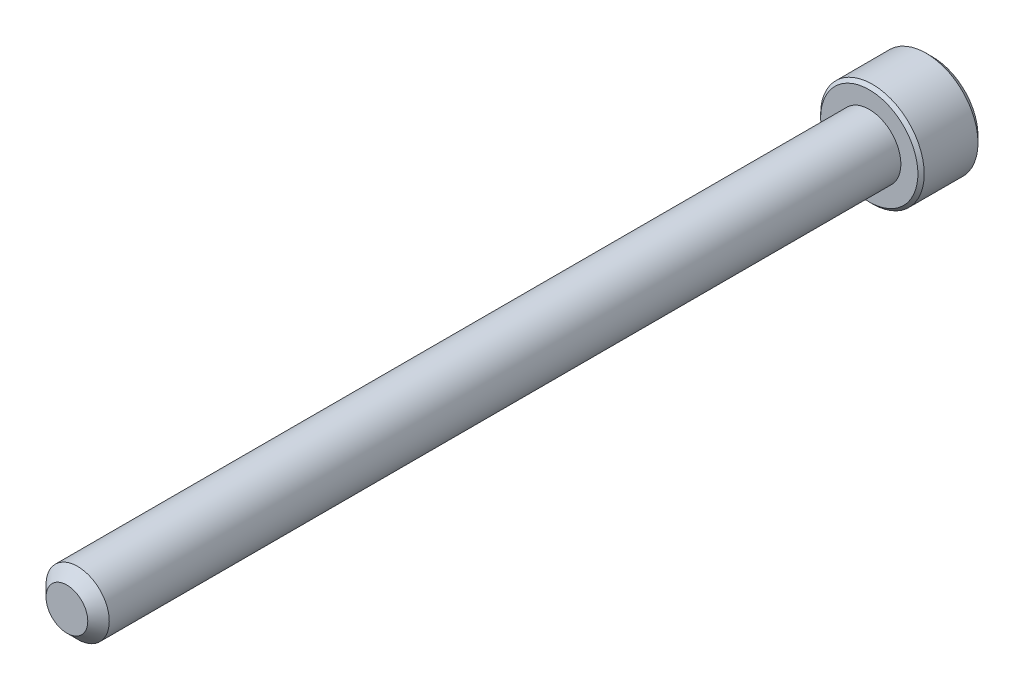
SolidWorks part; units mm, degrees
ref_plane "Front Plane" through (0, 0, 0) normal (0, 0, 1) x (1, 0, 0)
ref_plane "Top Plane" through (0, 0, 0) normal (0, 1, 0) x (1, 0, 0)
ref_plane "Right Plane" through (0, 0, 0) normal (1, 0, 0) x (0, 0, -1)
sketch "Sketch1" plane through (0, 0, 0) normal (0, 0, 1) x (1, 0, 0)
  line L0 (0, 1.7526) -> (0, -1.7526) construction
  circle A0 centre (0, 0) radius 1.7526
  dimension "OD" = 3.5052
extrude "Extrude1" add sketch "Sketch1" against normal blind 44.45
sketch "Sketch2" plane through (0, 0, 0) normal (0, 0, 1) x (1, 0, 0)
  circle A0 centre (0, 0) radius 1.7526 construction
  circle A1 centre (0, 0) radius 1.7526
curve "Helix/Spiral1" pitch 0.7937 height 20.6375 turns 26 parameters "pitch"=0.7937
chamfer "Chamfer3" distance 0.5953 angle 45 1 edges at (1.7526, 0, 0)
sketch "Sketch3" plane through (0, 0, 0) normal (1, 0, 0) x (0, 0, -1)
  line L0 (-0.6945, 1.7526) -> (-0.3969, 1.237)
  line L1 (-0.3969, 1.237) -> (-0.2977, 1.237)
  line L2 (-0.2977, 1.237) -> (0, 1.7526)
  line L3 (-0.6945, 1.7526) -> (0, 1.7526)
  line L4 (-0.3473, 1.7526) -> (-0.3473, 1.237) construction
  line L5 (-0.5457, 1.4948) -> (-0.1488, 1.4948) construction
  line L6 (0, 1.7526) -> (0, -1.7526) construction
  dimension "D1" = 0.0992
  dimension "D2" = 0.3969
  dimension "D3" = 60
sweep "Cut-Sweep1" [suppressed] cut profiles "Sketch3" path "Helix/Spiral1"
sketch "Sketch5" plane through (0, 0, 0) normal (1, 0, 0) x (0, 0, -1)
  line L1 (44.45, 1.7526) -> (19.05, 1.7526)
  line L2 (44.45, 1.7526) -> (44.45, 0)
  line L3 (44.45, 0) -> (19.05, 0)
  line L4 (19.05, 1.7526) -> (19.05, 0) construction
  line L6 (0, 0) -> (9.9695, 0) construction
  line L8 (19.05, 1.7526) -> (17.2974, 0)
  line L9 (17.2974, 0) -> (19.05, 0)
  line L10 (44.45, -1.7526) -> (44.45, 1.7526) construction
  dimension "Thread min" = 19.05
  dimension "D1" = 45
revolve "partially thread" add sketch "Sketch5" angle 360 about L6
sketch "Sketch6" plane through (0, 0, -44.45) normal (0, 0, -1) x (-1, 0, 0)
  circle A0 centre (0, 0) radius 2.8702
  dimension "head dia" = 5.7404
extrude "Extrude2" add sketch "Sketch6" along normal blind 3.5052
sketch "Sketch7" plane through (0, 0, -47.9552) normal (0, 0, -1) x (-1, 0, 0)
  line L1 (0, 1.604) -> (-1.3891, 0.802)
  line L2 (-1.3891, 0.802) -> (-1.3891, -0.802)
  line L3 (-1.3891, -0.802) -> (0, -1.604)
  line L4 (0, -1.604) -> (1.3891, -0.802)
  line L5 (1.3891, -0.802) -> (1.3891, 0.802)
  line L6 (1.3891, 0.802) -> (0, 1.604)
  circle A0 centre (0, 0) radius 1.3891 construction
  dimension "hex dia" = 2.7781
extrude "Cut-Extrude1" cut sketch "Sketch7" against normal blind 2.0836
sketch "Sketch8" plane through (0, 0, -47.9552) normal (0, 0, -1) x (-1, 0, 0)
  circle A0 centre (0, 0) radius 1.604
extrude "Cut-Extrude2" cut sketch "Sketch8" against normal blind 0.3505 draft 45
chamfer "Chamfer1" distance 0.3505 angle 45 1 edges at (-2.8702, 0, -47.9552)
chamfer "Chamfer2" distance 0.1753 angle 45 1 edges at (-2.8702, 0, -44.45)
sketch "Sketch9" plane through (0, 0, 0) normal (1, 0, 0) x (0, 0, -1)
  line L0 (0, 1.7526) -> (0, -1.7526) construction
  line L1 (4.3656, 1.7526) -> (4.3656, -1.7526) construction
  line L2 (44.45, 2.8702) -> (44.45, -2.8702) construction
  line L3 (47.9552, 2.8702) -> (47.9552, -2.8702) construction
  line L4 (47.9552, 0) -> (0, 0) construction
  line L5 (61.6852, 1.7526) -> (61.6852, -1.7526) construction
  dimension "D1" = 4.3656
  dimension "D2" = 3.5052
  dimension "D3" = 5.7404
  dimension "D4" = 44.45
  dimension "Thread Length" = 61.6852
equation "\"D3@Helix/Spiral1\" = \"Thread min@Sketch5\"+(\"pitch@Helix/Spiral1\"*2)"
equation "\"D1@Sketch3\" = \"pitch@Helix/Spiral1\"*.125"
equation "\"D2@Sketch3\" = \"pitch@Helix/Spiral1\"*.5"
equation "\"D1@Cut-Extrude1\" = \"hex dia@Sketch7\"*.75"
equation "\"D1@Chamfer1\" = \"head depth@Extrude2\"/10"
equation "\"D1@Sketch9\" = \"pitch@Helix/Spiral1\"*5.5"
equation "\"D1@Chamfer2\" = \"D1@Chamfer1\"/2"
equation "\"D1@Cut-Extrude2\" = \"D1@Chamfer2\"*2"
equation "\"D1@Chamfer3\" = \"pitch@Helix/Spiral1\"*.750"
equation "\"D2@Sketch9\" = \"head depth@Extrude2\""
equation "\"D3@Sketch9\" = \"head dia@Sketch6\""
equation "\"D4@Sketch9\" = \"screw length@Extrude1\""
